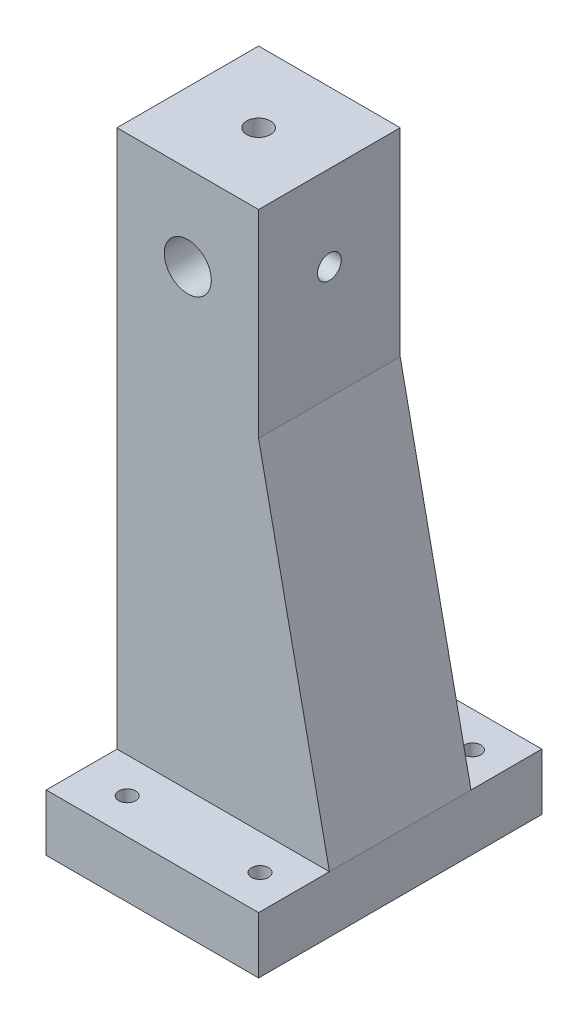
SolidWorks part; units mm, degrees
ref_plane "Front Plane" through (0, 0, 0) normal (0, 0, 1) x (1, 0, 0)
ref_plane "Top Plane" through (0, 0, 0) normal (0, 1, 0) x (1, 0, 0)
ref_plane "Right Plane" through (0, 0, 0) normal (1, 0, 0) x (0, 0, -1)
sketch "Croquis1" plane through (0, 0, 0) normal (0, 1, 0) x (1, 0, 0)
  line L0 (-25, -12.5) -> (-25, 12.5)
  line L1 (-25, -12.5) -> (25, -12.5)
  line L2 (-25, 12.5) -> (25, 12.5)
  line L3 (25, -12.5) -> (25, 12.5)
  line L4 (-25, -12.5) -> (25, 12.5) construction
  line L5 (-25, 12.5) -> (25, -12.5) construction
  line L6 (-12.5, 12.5) -> (-12.5, -12.5)
  line L7 (12.5, 12.5) -> (12.5, -12.5)
  line L8 (25, 12.5) -> (25, 25)
  line L9 (25, 25) -> (-25, 25)
  line L10 (-25, 25) -> (-25, 12.5)
  line L11 (25, -12.5) -> (25, -25)
  line L12 (25, -25) -> (-25, -25)
  line L13 (-25, -25) -> (-25, -12.5)
  point P1 (0, 0)
  dimension "D1" = 50
  dimension "D2" = 25
  dimension "D3" = 12.5
  dimension "D4" = 12.5
  dimension "D5" = 12.5
  dimension "D6" = 12.5
extrude "Saliente-Extruir1" add sketch "Croquis1" along normal blind 10 contours L6 L2 L0 L1 | L2 L7 L1 L3 | L7 L2 L6 L1 region at (-18.75, 0, 0) region at (0, 0, 0) region at (18.75, 0, 0)
extrude "Saliente-Extruir2" add sketch "Croquis1<3>" along normal blind 105 contours L7 L2 L6 L1 region at (0, 0, 0)
sketch "Croquis1<3>" plane through (0, 0, 0) normal (0, 1, 0) x (1, 0, 0) same geometry as "Croquis1"
sketch "Croquis2" plane through (0, 0, 12.5) normal (0, 0, 1) x (1, 0, 0)
  line L0 (-12.5, 105) -> (12.5, 105) construction
  line L1 (-12.5, 105) -> (-12.5, 10) construction
  circle A0 centre (0, 90) radius 4.15
  dimension "D1" = 8.3
  dimension "D2" = 15
  dimension "D3" = 12.5
extrude "Cortar-Extruir1" cut sketch "Croquis2" against normal blind 60
sketch "Croquis3" plane through (12.5, 0, 0) normal (1, 0, 0) x (0, 0, -1)
  line L0 (12.5, 105) -> (-12.5, 105) construction
  line L1 (-12.5, 105) -> (-12.5, 10) construction
  circle A0 centre (0, 90) radius 2.1
  dimension "D1" = 4.2
  dimension "D2" = 15
  dimension "D3" = 12.5
extrude "Cortar-Extruir2" cut sketch "Croquis3" against normal blind 10
extrude "Saliente-Extruir3" add sketch "Croquis1<4>" along normal blind 10 contours L9 L10 L2 L8 | L13 L12 L11 L1 region at (0, 0, 18.75) region at (0, 0, -18.75)
sketch "Croquis1<4>" plane through (0, 0, 0) normal (0, 1, 0) x (1, 0, 0) same geometry as "Croquis1"
sketch "Croquis5" plane through (0, 10, 0) normal (0, 1, 0) x (1, 0, 0)
  line L0 (8.5435, 25) -> (8.5435, 12.5) construction
  line L1 (25, 25) -> (-25, 25) construction
  line L2 (-12.5, 12.5) -> (12.5, 12.5) construction
  line L3 (8.5435, -12.5) -> (8.5435, -25) construction
  line L4 (-12.5, -12.5) -> (12.5, -12.5) construction
  line L5 (25, -25) -> (-25, -25) construction
  line L6 (-25, -25) -> (-25, 25) construction
  circle A0 centre (-4.4565, 18.75) radius 1.5
  circle A1 centre (-4.4565, -18.75) radius 1.5
  point P17 (8.5435, -18.75)
  point P19 (8.5435, 18.75)
  dimension "D1" = 3
  dimension "D2" = 3
  dimension "D3" = 13
  dimension "D4" = 13
  dimension "D5" = 33.5435
extrude "Cortar-Extruir4" cut sketch "Croquis5" against normal blind 10
sketch "Croquis6" plane through (0, 10, 0) normal (0, 1, 0) x (1, 0, 0)
  line L0 (-12.5, 25) -> (-12.5, 12.5)
  line L1 (25, 25) -> (-25, 25) construction
  line L2 (-12.5, 12.5) -> (-12.5, -12.5)
  line L3 (-12.5, -12.5) -> (-12.5, -25)
  line L4 (25, -25) -> (-25, -25) construction
  line L5 (-12.5, -25) -> (-25, -25)
  line L6 (-25, -25) -> (-25, 25)
  line L7 (-25, 25) -> (-12.5, 25)
extrude "Cortar-Extruir7" cut sketch "Croquis6" against normal blind 10
sketch "Croquis8" plane through (0, 105, 0) normal (0, 1, 0) x (1, 0, 0)
  circle A0 centre (0, 0) radius 2.1
  dimension "D1" = 4.2
extrude "Cortar-Extruir9" cut sketch "Croquis8" against normal blind 15
sketch "Croquis9" plane through (0, 10, 0) normal (0, 1, 0) x (1, 0, 0)
  line L0 (25, -25) -> (25, 25) construction
  line L1 (25, -25) -> (-12.5, -25) construction
  line L2 (25, 25) -> (-12.5, 25) construction
  circle A0 centre (19, -18.75) radius 1.5
  circle A1 centre (19, 18.75) radius 1.5
  dimension "D2" = 6
  dimension "D3" = 3
  dimension "D4" = 3
  dimension "D1" = 6
  dimension "D5" = 6.25
  dimension "D6" = 6.25
extrude "Cortar-Extruir10" cut sketch "Croquis9" against normal blind 10
sketch "Croquis10" plane through (0, 0, 0) normal (0, 0, 1) x (1, 0, 0)
  line L0 (0, 0) -> (0, 10) construction
  line L1 (0, 10) -> (12.5, 10) construction
  line L2 (12.5, 10) -> (25, 10)
  line L3 (25, 10) -> (12.5, 70)
  line L4 (12.5, 70) -> (12.5, 10)
  dimension "D1" = 10
  dimension "D2" = 12.5
  dimension "D3" = 12.5
  dimension "D4" = 60
extrude "Saliente-Extruir4" add sketch "Croquis10" along normal mid plane 25
